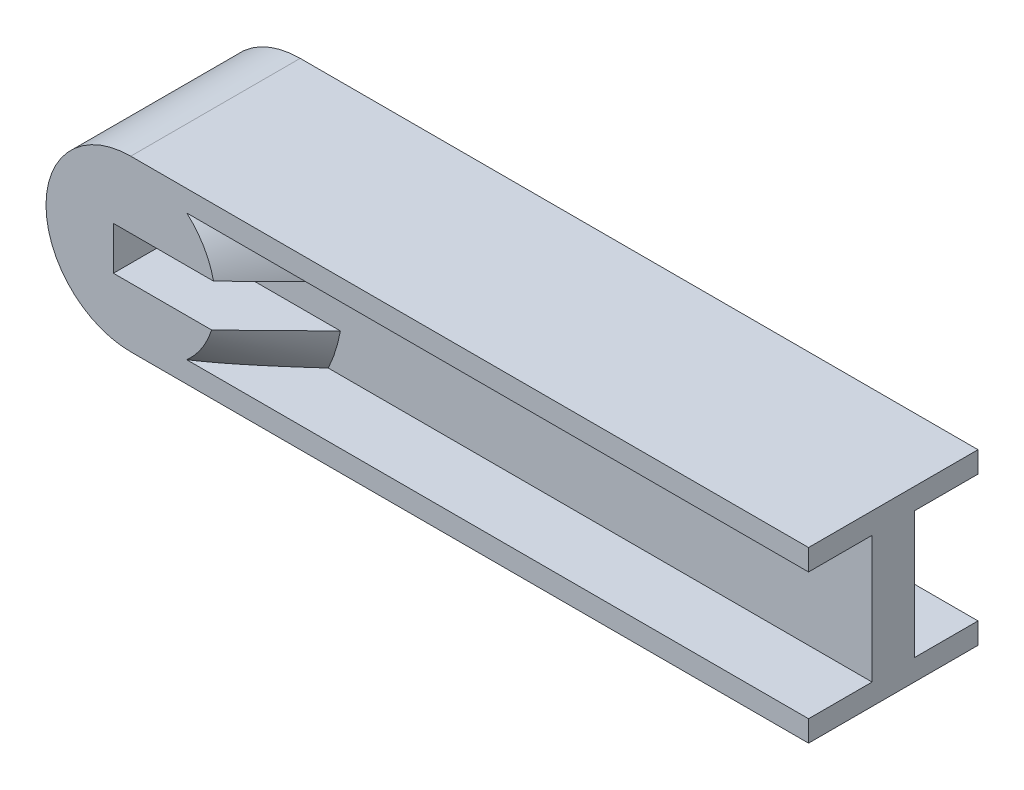
SolidWorks part; units mm, degrees
ref_plane "Front Plane" through (0, 0, 0) normal (0, 0, 1) x (1, 0, 0)
ref_plane "Top Plane" through (0, 0, 0) normal (0, 1, 0) x (1, 0, 0)
ref_plane "Right Plane" through (0, 0, 0) normal (1, 0, 0) x (0, 0, -1)
sketch "Sketch1" plane through (0, 0, 0) normal (0, 1, 0) x (1, 0, 0)
  line L0 (-40, -10) -> (-40, 10)
  line L1 (-40, -10) -> (40, -10)
  line L2 (-40, 10) -> (40, 10)
  line L3 (40, -10) -> (40, 10)
  line L4 (-40, -10) -> (40, 10) construction
  line L5 (-40, 10) -> (40, -10) construction
  point P1 (0, 0)
  dimension "D1" = 80
  dimension "D2" = 20
extrude "Boss-Extrude1" add sketch "Sketch1" along normal mid plane 20
sketch "Sketch2" plane through (0, 0, 0) normal (0, 1, 0) x (1, 0, 0)
  line L0 (40, 10) -> (40, 2.5)
  line L1 (40, -10) -> (-40, -10)
  line L2 (-40, -10) -> (-40, -2.5)
  line L3 (-40, 10) -> (40, 10)
  line L4 (-40, 2.5) -> (40, 2.5)
  line L6 (40, -2.5) -> (-40, -2.5)
  line L8 (0, 2.5) -> (0, -2.5) construction
  line L9 (-40, 2.5) -> (-40, 10)
  line L10 (40, -2.5) -> (40, -10)
  point P14 (0, 0)
  dimension "D1" = 5
extrude "Cut-Extrude1" cut sketch "Sketch2" against normal mid plane 15
sketch "Sketch3" plane through (0, 0, 0) normal (0, 0, 1) x (1, 0, 0)
  line L20 (-40, -7.5) -> (-40, 7.5) construction
  circle A5 centre (-40, 0) radius 10
extrude "Boss-Extrude2" add sketch "Sketch3" along normal mid plane 20
chamfer "Chamfer1" distance 7.5 angle 45 2 edges at (-30, 0, -2.5) (-30, 0, 2.5)
sketch "Sketch8" plane through (0, 0, 10) normal (0, 0, 1) x (1, 0, 0)
  line L5 (-42.0429, 2.1132) -> (-17.642, 2.1132)
  line L6 (-42.0429, 2.1132) -> (-42.0429, -2.9888)
  line L7 (-42.0429, -2.9888) -> (-17.642, -2.9888)
  line L8 (-17.642, 2.1132) -> (-17.642, -2.9888)
extrude "Cut-Extrude2" cut sketch "Sketch8" against normal up to surface (7.5 mm away) up to face at (8.3278, 0, 2.5)
sketch "Sketch9" plane through (0, 0, -10) normal (0, 0, -1) x (-1, 0, 0)
  circle A0 centre (40, 0) radius 3.8
  dimension "D1" = 7.6
extrude "Cut-Extrude3" cut sketch "Sketch9" against normal blind 5
